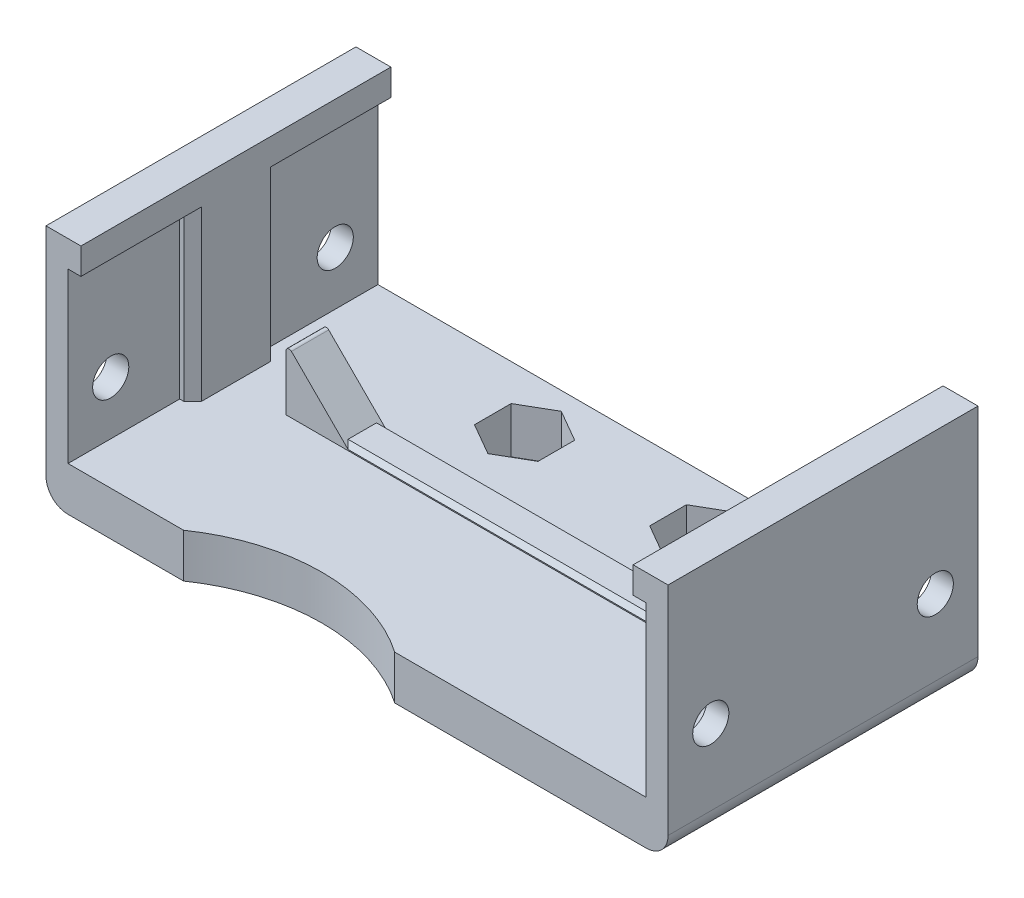
SolidWorks part; units mm, degrees
ref_plane "Front Plane" through (0, 0, 0) normal (0, 0, 1) x (1, 0, 0)
ref_plane "Top Plane" through (0, 0, 0) normal (0, 1, 0) x (1, 0, 0)
ref_plane "Right Plane" through (0, 0, 0) normal (1, 0, 0) x (0, 0, -1)
sketch "Sketch1" plane through (0, 0, 0) normal (0, 0, 1) x (1, 0, 0)
  line L0 (0, 21.81) -> (3.19, 21.81)
  line L1 (0, 21.81) -> (0, 2)
  line L2 (2, 0) -> (54.8, 0)
  line L3 (56.8, 21.81) -> (56.8, 2)
  line L18 (53.61, 21.81) -> (56.8, 21.81)
  line L54 (53.61, 4.02) -> (53.61, 21.81)
  line L55 (3.19, 21.81) -> (3.19, 4.02)
  line L57 (3.19, 4.02) -> (53.61, 4.02)
  arc A0 (54.8, 0) -> (56.8, 2) centre (54.8, 2) ccw
  arc A1 (0, 2) -> (2, 0) centre (2, 2) ccw
extrude "Boss-Extrude1" add sketch "Sketch1" along normal blind 28.3
sketch "Sketch2" plane through (0, 0, 0) normal (0, 0, 1) x (1, 0, 0)
  line L0 (2.01, 19.4) -> (54.79, 19.4)
  line L1 (2.01, 19.4) -> (2.01, 4.02)
  line L2 (2.01, 4.02) -> (54.79, 4.02)
  line L3 (54.79, 19.4) -> (54.79, 4.02)
extrude "Cut-Extrude1" cut sketch "Sketch2" along normal blind 10.2
extrude "Cut-Extrude2" cut sketch "Sketch2<2>" against normal blind 10.2 from surface starting at face at (28.4, 9.8452, 28.3)
sketch "Sketch2<2>" plane through (0, 0, 0) normal (0, 0, 1) x (1, 0, 0) same geometry as "Sketch2"
sketch "Sketch3" plane through (0, 0, 0) normal (-1, 0, 0) x (0, 0, 1)
  circle A0 centre (3.9, 8.91) radius 1.65
  circle A1 centre (24.4, 8.91) radius 1.65
extrude "Cut-Extrude3" cut sketch "Sketch3" against normal up to surface (56.8 mm away) up to face at (56.8, 11.905, 14.15)
sketch "Sketch4" plane through (0, 0, 0) normal (0, 0, 1) x (1, 0, 0)
  line L0 (8.6121, 9.286) -> (13.3782, 4.52)
  line L3 (8.1, 4.02) -> (48.7, 4.02)
  line L5 (13.3782, 4.52) -> (43.4218, 4.52)
  line L6 (43.4218, 4.52) -> (48.1879, 9.286)
  line L12 (8.1, 4.02) -> (8.1, 9.0739)
  line L13 (48.7, 4.02) -> (48.7, 9.0739)
  arc A0 (48.7, 9.0739) -> (48.1879, 9.286) centre (48.4, 9.0739) ccw
  arc A1 (8.1, 9.0739) -> (8.6121, 9.286) centre (8.4, 9.0739) cw
extrude "Boss-Extrude2" add sketch "Sketch4" along normal blind 3.4 from offset 11.1
sketch "Sketch5" plane through (0, 0, 0) normal (0, -1, 0) x (1, 0, 0)
  line L0 (12.5563, 28.3) -> (31.8437, 28.3)
  arc A2 (12.5563, 28.3) -> (31.8437, 28.3) centre (22.2, 42.3) ccw
extrude "Cut-Extrude4" cut sketch "Sketch5" against normal up to surface (4.02 mm away) up to face at (28.4, 4.02, 12.8)
sketch "Sketch6" plane through (0, 0, 0) normal (0, -1, 0) x (1, 0, 0)
  line L62 (16.4, 10) -> (24.4, 10)
  line L67 (15.4, 9) -> (15.4, 1)
  line L72 (16.4, 0) -> (24.4, 0)
  line L73 (25.4, 9) -> (25.4, 1)
  line L74 (15.4, 9) -> (16.4, 10)
  line L75 (24.4, 10) -> (25.4, 9)
  line L76 (24.4, 0) -> (25.4, 1)
  line L77 (15.4, 1) -> (16.4, 0)
  line L79 (32.4, 10) -> (40.4, 10)
  line L80 (31.4, 9) -> (31.4, 1)
  line L81 (32.4, 0) -> (40.4, 0)
  line L82 (41.4, 9) -> (41.4, 1)
  line L83 (31.4, 9) -> (32.4, 10)
  line L84 (40.4, 10) -> (41.4, 9)
  line L85 (40.4, 0) -> (41.4, 1)
  line L86 (31.4, 1) -> (32.4, 0)
  circle A6 centre (20.4, 5) radius 1.65
  circle A7 centre (36.4, 5) radius 1.65
extrude "Boss-Extrude3" add sketch "Sketch6" along normal blind 3.2
sketch "Sketch8" plane through (0, 4.02, 0) normal (0, -1, 0) x (1, 0, 0)
  line L0 (23.3, 6.6743) -> (20.4, 8.3486)
  line L7 (20.4, 8.3486) -> (17.5, 6.6743)
  line L8 (17.5, 6.6743) -> (17.5, 3.3257)
  line L21 (17.5, 3.3257) -> (20.4, 1.6514)
  line L22 (20.4, 1.6514) -> (23.3, 3.3257)
  line L23 (23.3, 3.3257) -> (23.3, 6.6743)
  line L25 (39.3, 6.6743) -> (36.4, 8.3486)
  line L26 (36.4, 8.3486) -> (33.5, 6.6743)
  line L27 (33.5, 6.6743) -> (33.5, 3.3257)
  line L28 (33.5, 3.3257) -> (36.4, 1.6514)
  line L29 (36.4, 1.6514) -> (39.3, 3.3257)
  line L30 (39.3, 3.3257) -> (39.3, 6.6743)
extrude "Cut-Extrude5" cut sketch "Sketch8" along normal offset from surface (4.22 mm away) 3 up to face at (20.4, -3.2, 5)
chamfer "Chamfer1" distance 0.4 angle 45 2 edges at (28.4, 4.52, 11.1) (28.4, 4.52, 14.5)
chamfer "Chamfer2" distance 0.8 angle 45 4 edges at (53.61, 11.71, 10.2) (53.61, 11.71, 18.1) (3.19, 11.71, 18.1) (3.19, 11.71, 10.2)
